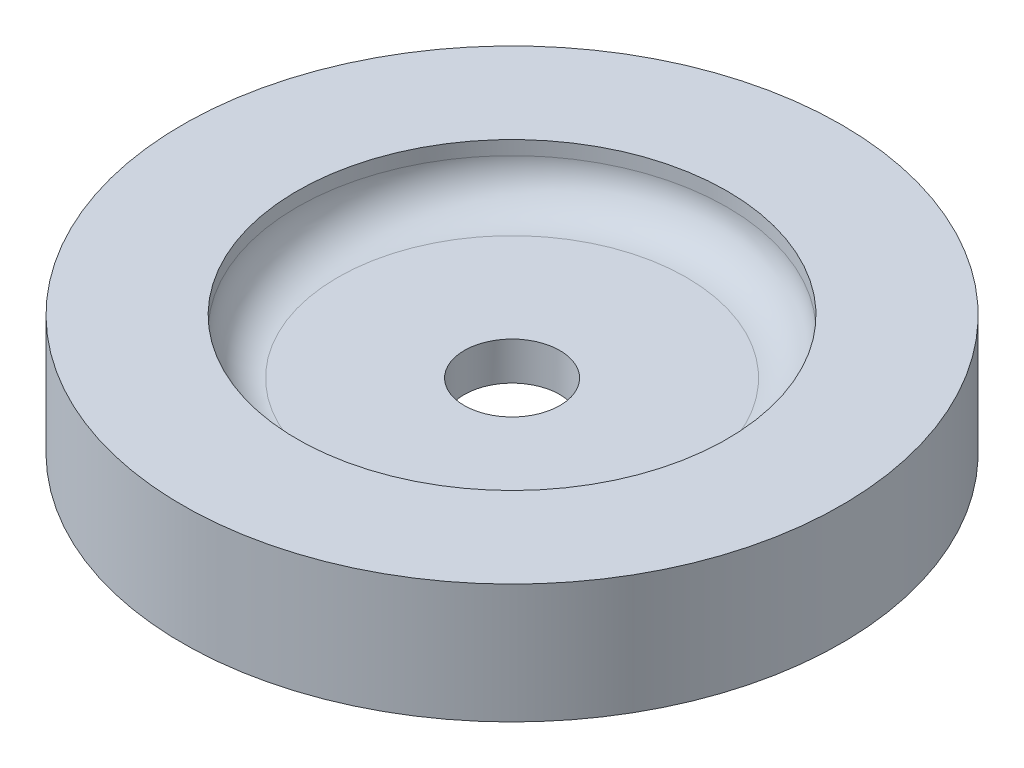
SolidWorks part; units mm, degrees
ref_plane "Front Plane" through (0, 0, 0) normal (0, 0, 1) x (1, 0, 0)
ref_plane "Top Plane" through (0, 0, 0) normal (0, 1, 0) x (1, 0, 0)
ref_plane "Right Plane" through (0, 0, 0) normal (1, 0, 0) x (0, 0, -1)
sketch "Sketch1" plane through (0, 0, 0) normal (0, 0, 1) x (1, 0, 0)
  line L0 (87.63, 0) -> (57.15, 0)
  line L1 (57.15, 0) -> (57.15, 7.0866)
  line L2 (57.15, 7.0866) -> (0, 7.0866)
  line L3 (0, 7.0866) -> (0, 17.2466)
  line L4 (0, 17.2466) -> (57.15, 17.2466)
  line L5 (57.15, 17.2466) -> (57.15, 31.75)
  line L6 (57.15, 31.75) -> (87.63, 31.75)
  line L9 (87.63, 31.75) -> (87.63, 0)
  point P10 (0, 12.1666)
  dimension "D1" = 10.16
  dimension "D2" = 87.63
  dimension "D3" = 57.15
  dimension "D4" = 57.15
  dimension "D5" = 31.75
  dimension "D6" = 7.0866
revolve "Revolve1" add sketch "Sketch1" angle 360 about L3
fillet "Fillet2" radius 10.795 2 edges at (0, 7.0866, -57.15) (0, 17.2466, -57.15)
hole_wizard "1 (1) Diameter Hole1" positions "Sketch8" profile "Sketch9" hole size "1" standard "ANSI Inch" end condition through all
sketch "Sketch8" plane through (0, 17.2466, 0) normal (0, 1, 0) x (1, 0, 0)
  point P0 (0, 0)
sketch "Sketch9" plane through (0, 17.2466, 0) normal (1, 0, 0) x (0, 0, 1)
  line L0 (0, 0) -> (0, 17.2466)
  line L1 (0, 17.2466) -> (12.7, 17.2466)
  line L2 (12.7, 17.2466) -> (12.7, 0)
  line L5 (12.7, 0) -> (0, 0)
  line L11 (0, -6.35) -> (0, 107.95) construction
  dimension "Thru Hole Dia." = 25.4
  dimension "Thru Hole Depth" = 17.2466
